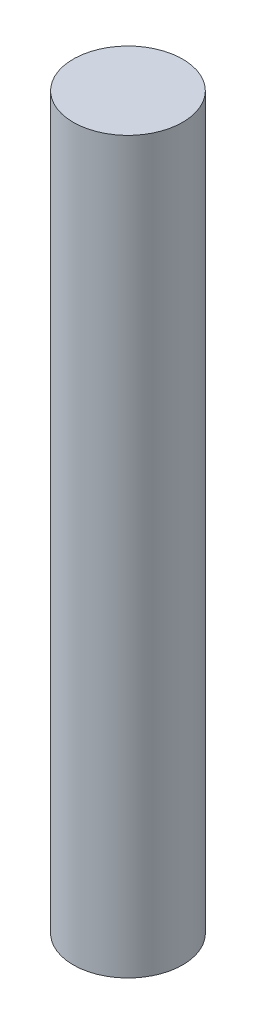
SolidWorks part; units mm, degrees
material "Galvanized Steel"
ref_plane "Front Plane" through (0, 0, 0) normal (0, 0, 1) x (1, 0, 0)
ref_plane "Top Plane" through (0, 0, 0) normal (0, 1, 0) x (1, 0, 0)
ref_plane "Right Plane" through (0, 0, 0) normal (1, 0, 0) x (0, 0, -1)
sketch "Sketch1" plane through (0, 0, 0) normal (0, 1, 0) x (1, 0, 0)
  circle A0 centre (0, 0) radius 9.525
  dimension "D1" = 19.05
extrude "Boss-Extrude1" add sketch "Sketch1" against normal blind 127
